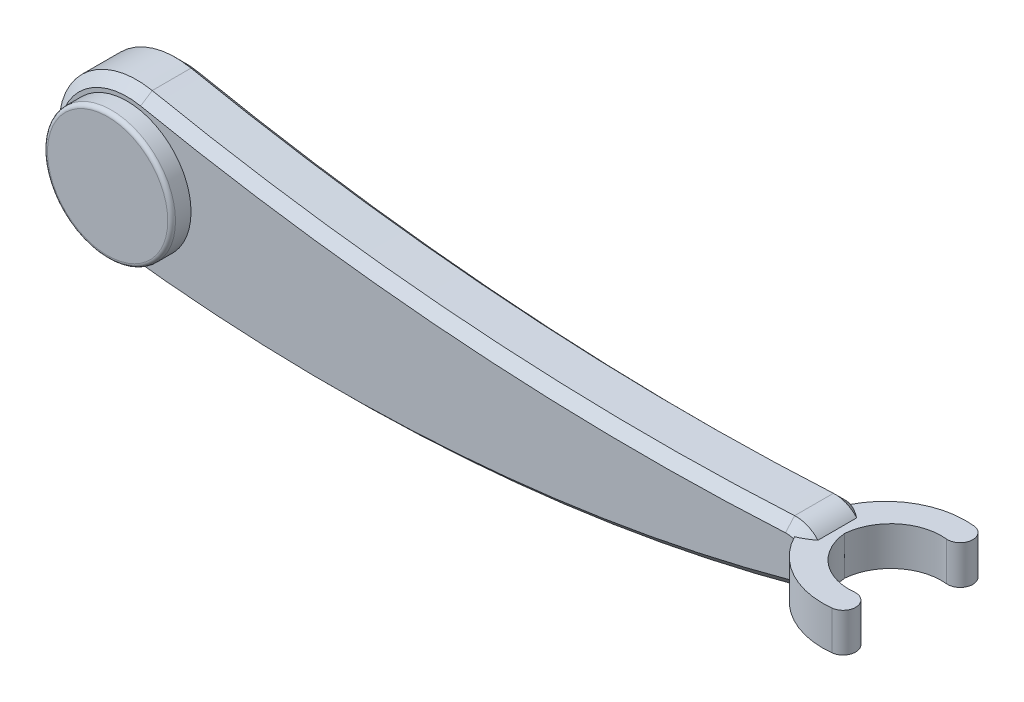
SolidWorks part; units mm, degrees
ref_plane "Front Plane" through (0, 0, 0) normal (0, 0, 1) x (1, 0, 0)
ref_plane "Top Plane" through (0, 0, 0) normal (0, 1, 0) x (1, 0, 0)
ref_plane "Right Plane" through (0, 0, 0) normal (1, 0, 0) x (0, 0, -1)
sketch "Sketch1" plane through (0, 0, 0) normal (0, 0, 1) x (1, 0, 0)
  line L0 (-85, 0) -> (85, 0) construction
  circle A0 centre (85, 0) radius 7.5
  circle A1 centre (-85, 0) radius 20
  arc A2 (-81.0058, 19.5971) -> (84.5871, 7.4886) centre (48.8051, 656.503) ccw
  arc A3 (-87.4615, -19.8479) -> (86.9844, -7.2327) centre (-32.0772, 426.7308) ccw
  point P4 (0, 0)
  dimension "D2" = 40
  dimension "D3" = 15
  dimension "D4" = 450
  dimension "D5" = 650
  dimension "D1" = 170
extrude "Boss-Extrude1" add sketch "Sketch1" along normal mid plane 15 contours A1 | A1 L0 A0 A2 | L0 A1 A3 A0 | A0 region at (-7.6395, 5.4148, 0) region at (-72.1313, -14.5633, 0) region at (-3.1113, -10.4688, 0) region at (79.7068, 5.0095, 0)
chamfer "Chamfer1" distance 2.5 angle 45 8 edges at (92.4025, 1.2054, -7.5) (1.4024, 8.2338, -7.5) (-104.7374, 3.2303, -7.5) (0.3802, -22.0971, -7.5) (-104.7374, 3.2303, 7.5) (1.4024, 8.2338, 7.5) (92.4025, 1.2054, 7.5) (0.3802, -22.0971, 7.5)
sketch "Sketch2" plane through (0, 0, 7.5) normal (0, 0, 1) x (1, 0, 0)
  circle A0 centre (-85, 0) radius 16.5
  dimension "D1" = 33
extrude "Boss-Extrude2" add sketch "Sketch2" along normal blind 5
sketch "Sketch3" plane through (0, 0, 12.5) normal (0, 0, 1) x (1, 0, 0)
  line L0 (-85, 0) -> (-88.9097, 0)
  line L1 (-86.0119, 3.7765) -> (-83.9881, -3.7765)
  line L2 (-88.3859, -1.9548) -> (-85, 0)
  line L4 (-87.9055, 2.6161) -> (-85, 0)
  line L5 (-85, 0) -> (-86.2082, 3.7183)
  line L6 (-81.7211, 2.1294) -> (-88.2789, -2.1294)
  line L7 (-83.4098, 3.5717) -> (-85, 0)
  line L8 (-85, 0) -> (-81.837, 2.298)
  line L9 (-81.9616, -2.4604) -> (-88.0384, 2.4604)
  line L10 (-81.1117, -0.4087) -> (-85, 0)
  line L11 (-85, 0) -> (-81.837, -2.298)
  line L12 (-86.4011, -3.65) -> (-83.5989, 3.65)
  line L13 (-84.1871, -3.8242) -> (-85, 0)
  line L14 (-85, 0) -> (-86.2082, -3.7183)
  line L15 (-88.9043, 0.2046) -> (-81.0957, -0.2046)
  arc A0 (-86.0119, 3.7765) -> (-88.9097, 0) centre (-88.9097, 3) cw
  arc A1 (-83.9881, -3.7765) -> (-88.3859, -1.9548) centre (-86.8859, -4.5529) ccw
  arc A2 (-88.2789, -2.1294) -> (-87.9055, 2.6161) centre (-89.9128, 0.3866) ccw
  arc A3 (-81.7211, 2.1294) -> (-86.2082, 3.7183) centre (-83.355, 4.6454) cw
  arc A4 (-88.0384, 2.4604) -> (-83.4098, 3.5717) centre (-86.1504, 4.7919) ccw
  arc A5 (-81.9616, -2.4604) -> (-81.837, 2.298) centre (-80.0736, -0.129) cw
  arc A6 (-83.5989, 3.65) -> (-81.1117, -0.4087) centre (-80.7982, 2.5749) ccw
  arc A7 (-86.4011, -3.65) -> (-81.837, -2.298) centre (-83.6004, -4.7251) cw
  arc A8 (-81.0957, -0.2046) -> (-84.1871, -3.8242) centre (-81.2527, -3.2005) ccw
  arc A9 (-88.9043, 0.2046) -> (-86.2082, -3.7183) centre (-89.0613, -2.7913) cw
  circle A10 centre (-85, 0) radius 2
  point P10 (-85, 0)
  point P38 (-85, 0)
  circle M17 centre (-85, 0) radius 16.5
  dimension "D3" = 3
  dimension "D5" = 4
  dimension "D1" = 30
  dimension "D2" = 0
  dimension "D4" = 5
extrude "Boss-Extrude3" add sketch "Sketch3" against normal blind 5 contours A9 L15 A8 M17 | A10 L14 A9 A8 L13 M17 | L1 A1 M17 | A0 L1 M17 | A10 A1 L2 M17 | A10 L0 A0 M17 | A10 L5 A3 A2 L4 M17 | A3 L6 A2 M17 | A10 L8 A5 A4 L7 M17 | A5 L9 A4 M17 | A10 L11 A7 A6 L10 M17 | A7 L12 A6 M17 region at (-101.0333, 0, 12.5)
fillet "Fillet1" radius 1 1 edges at (-68.5, 0, 12.5)
sketch "Sketch5" plane through (0, 0, -7.5) normal (0, 0, -1) x (-1, 0, 0)
  circle A0 centre (85, 0) radius 5
  dimension "D1" = 10
extrude "Boss-Extrude4" add sketch "Sketch5" along normal blind 10
sketch "Sketch6" plane through (0, 0, 0) normal (0, 1, 0) x (1, 0, 0)
  line L0 (0, 0) -> (92.5, 0) construction
  line L1 (92.5, -5) -> (92.5, 5) construction
  line L3 (84.5871, -5) -> (84.5871, 5) construction
  arc A0 (92.5, 0) -> (106.8452, 11.8609) centre (105.5251, -1.1479) cw
  arc A1 (84.5871, 0) -> (107.5303, 18.3226) centre (105.2451, -2.3417) cw
  arc A2 (107.5303, 18.3226) -> (106.8452, 11.8609) centre (107.1732, 15.0933) cw
  arc A3 (107.5303, -18.3226) -> (106.8452, -11.8609) centre (107.1732, -15.0933) ccw
  arc A4 (84.5871, 0) -> (107.5303, -18.3226) centre (105.2451, 2.3417) ccw
  arc A5 (92.5, 0) -> (106.8452, -11.8609) centre (105.5251, 1.1479) ccw
extrude "Boss-Extrude5" add sketch "Sketch6" along normal mid plane 10
